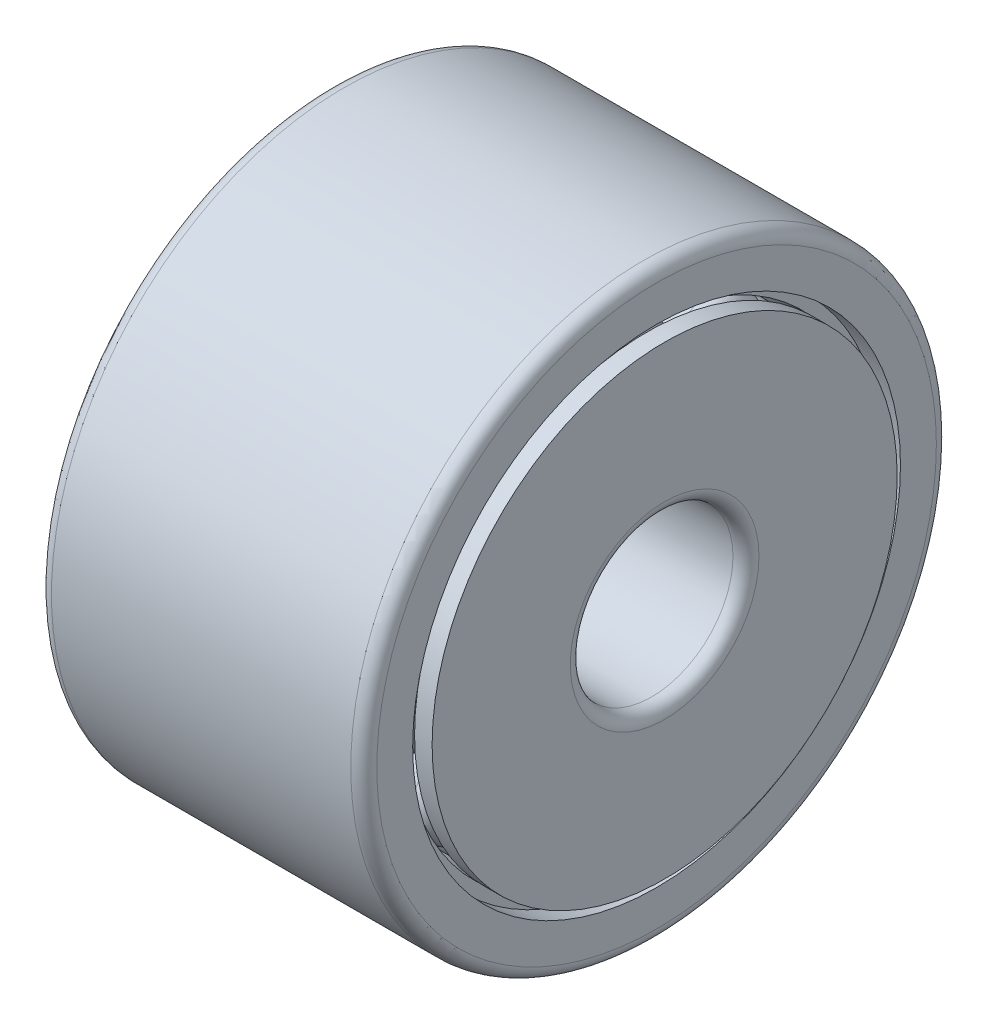
SolidWorks part; units mm, degrees
ref_plane "Plane1" through (0, 0, 0) normal (0, 0, 1) x (1, 0, 0)
ref_plane "Plane2" through (0, 0, 0) normal (0, 1, 0) x (1, 0, 0)
ref_plane "Plane3" through (0, 0, 0) normal (1, 0, 0) x (0, 0, -1)
sketch "Clipboard" plane through (0, 0, 0) normal (0, 0, 1) x (1, 0, 0)
  line L0 (-10, 0) -> (10, 0) construction
  line L1 (0, 0) -> (27.0344, -5.7463)
  line L2 (0, 0) -> (22.4793, 28.7722)
  line L3 (0, 0) -> (27.9428, -35.7651)
  line L4 (0, 0) -> (-22.3471, -0.7804)
  dimension "Race_OD" = 45.3866
  dimension "Race_ID" = 27.6384
sketch "OutRacSke" plane through (0, 0, 0) normal (0, 0, 1) x (1, 0, 0)
  line L0 (-14.0229, 22.6933) -> (-14.0229, 23.8026)
  line L1 (-14.0229, 23.8026) -> (-15.875, 23.8026)
  line L2 (-15.875, 23.8026) -> (-15.875, 27.305)
  line L3 (-14.605, 28.575) -> (14.605, 28.575)
  line L4 (15.875, 27.305) -> (15.875, 23.8026)
  line L5 (15.875, 23.8026) -> (14.0229, 23.8026)
  line L6 (14.0229, 23.8026) -> (14.0229, 22.6933)
  line L7 (14.0229, 22.6933) -> (-14.0229, 22.6933)
  line L8 (-7.9375, 0) -> (7.9375, 0) construction
  arc A0 (-15.875, 27.305) -> (-14.605, 28.575) centre (-14.605, 27.305) cw
  arc A1 (14.605, 28.575) -> (15.875, 27.305) centre (14.605, 27.305) cw
  dimension "D1" = 14.0229
  dimension "Race_OD" = 45.3866
  dimension "Cyl_Len" = 28.0458
revolve "OuterRace" add sketch "OutRacSke" angle 360 about L8
sketch "RolDetSke" plane through (0, 0, 0) normal (0, 0, 1) x (1, 0, 0)
  line L0 (-14.0229, 20.9188) -> (-14.0229, 18.2562)
  line L1 (-14.0229, 18.2562) -> (14.0229, 18.2562)
  line L2 (14.0229, 18.2562) -> (14.0229, 20.9188)
  line L3 (12.2479, 22.6938) -> (-12.2479, 22.6938)
  line L4 (-28.575, 18.2562) -> (28.575, 18.2562) construction
  arc A0 (14.0229, 20.9188) -> (12.2479, 22.6938) centre (12.2479, 20.9188) ccw
  arc A1 (-12.2479, 22.6938) -> (-14.0229, 20.9188) centre (-12.2479, 20.9188) ccw
  dimension "Cyl_Len" = 28.0458
  dimension "radius" = 1.775
  dimension "Roller_diameter" = 8.8751
revolve "RollerDetailed" add sketch "RolDetSke" angle 360 about L4
ref_axis "Axis1" through (-50, 0, 0) along (1, 0, 0)
pattern_circular "RollersDetailed" count 12 every 30 about axis through (-50, 0, 0) along (1, 0, 0) of "RollerDetailed", "OuterRace"
sketch "RolSimSke" plane through (0, 25.4, 0) normal (0, 0, 1) x (1, 0, 0)
  line L0 (-14.0229, -4.4807) -> (-14.0229, -9.8058)
  line L1 (-25.4, -25.4) -> (25.4, -25.4) construction
  line L2 (14.0229, -9.8058) -> (14.0229, -4.4807)
  line L3 (12.2479, -2.7057) -> (-12.2479, -2.7057)
  line L5 (12.2479, -11.5808) -> (-12.2479, -11.5808)
  arc A0 (14.0229, -4.4807) -> (12.2479, -2.7057) centre (12.2479, -4.4807) ccw
  arc A1 (-12.2479, -2.7057) -> (-14.0229, -4.4807) centre (-12.2479, -4.4807) ccw
  arc A2 (14.0229, -9.8058) -> (12.2479, -11.5808) centre (12.2479, -9.8058) cw
  arc A3 (-12.2479, -11.5808) -> (-14.0229, -9.8058) centre (-12.2479, -9.8058) cw
  dimension "radius" = 1.775
  dimension "Roller_diameter" = 8.8751
  dimension "Cyl_Len" = 28.0458
revolve "RollersSimplified" [suppressed] add sketch "RolSimSke" angle 360 about L1
sketch "InsRacSke" plane through (0, 0, 0) normal (0, 0, 1) x (1, 0, 0)
  line L0 (-14.949, 13.8192) -> (-14.949, 22.6933)
  line L1 (-14.949, 22.6933) -> (-16.6624, 22.6933)
  line L2 (-16.6624, 22.6933) -> (-16.6624, 9.2075)
  line L3 (-15.3924, 7.9375) -> (-0.84, 7.9375)
  line L4 (0.84, 7.9375) -> (15.3924, 7.9375)
  line L5 (16.6624, 9.2075) -> (16.6624, 22.6933)
  line L6 (16.6624, 22.6933) -> (14.949, 22.6933)
  line L7 (14.949, 22.6933) -> (14.949, 13.8192)
  line L8 (14.949, 13.8192) -> (-14.949, 13.8192)
  line L9 (-7.9375, 0) -> (7.9375, 0) construction
  arc A0 (-16.6624, 9.2075) -> (-15.3924, 7.9375) centre (-15.3924, 9.2075) ccw
  arc A1 (-0.84, 7.9375) -> (0.84, 7.9375) centre (0, 6.985) cw
  arc A2 (15.3924, 7.9375) -> (16.6624, 9.2075) centre (15.3924, 9.2075) ccw
  dimension "radius" = 1.27
  dimension "Bore" = 15.875
  dimension "halfWidth" = 16.6624
  dimension "Race_OD" = 45.3866
  dimension "Race_ID" = 27.6384
  dimension "SlotWidth" = 29.8979
revolve "InnerRace" add sketch "InsRacSke" angle 360 about L9
equation "\"halfWidth@OutRacSke\" =  \"Width@OutRacSke\" / 2"
equation "\"CLdia@Clipboard\" =  ( \"Race_OD@Clipboard\" + \"Race_ID@Clipboard\" )  / 2"
equation "\"CLRad@RolDetSke\" = ( \"Race_OD@Clipboard\" + \"Race_ID@Clipboard\" )  / 4"
equation "\"Roller_diameter@RolDetSke\" =  ( \"Race_OD@Clipboard\" -  \"Race_ID@Clipboard\" )  / 2 + .001"
equation "\"Roller_diameter@RolSimSke\" = ( \"Race_OD@Clipboard\" -  \"Race_ID@Clipboard\" )  / 2 + .001"
equation "\"radius@RolDetSke\" = \"Roller_diameter@RolDetSke\" / 5"
equation "\"radius@RolSimSke\" = \"Roller_diameter@RolSimSke\" / 5"
equation "\"Cyl_Len@OutRacSke\" = \"Cyl_Len@RolDetSke\""
equation "\"Cyl_Len@RolSimSke\" = \"Cyl_Len@RolDetSke\""
equation "\"halfCylLen@RolDetSke\" = \"Cyl_Len@RolDetSke\" / 2"
equation "\"offset@InsRacSke\" = \"radius@InsRacSke\" * 0.75"
equation "\"SlotWidth@InsRacSke\" =  ( \"Width@OutRacSke\" + \"Cyl_Len@RolDetSke\" )  / 2"
equation "\"halfSlotWidth@InsRacSke\" = \"SlotWidth@InsRacSke\" / 2"
equation "\"D1@OutRacSke\" = \"Cyl_Len@OutRacSke\" / 2"
equation "\"Max_count@Clipboard\" = int( 3.14159265 / atn(( \"Roller_diameter@RolDetSke\" / 2) / sqr( \"CLRad@RolDetSke\"  *  \"CLRad@RolDetSke\" - ( \"Roller_diameter@RolDetSke\" / 2) *  ( \"Roller_diameter@RolDetSke\" / 2))))"
equation "\"Max_count@Clipboard\" = ((sgn( \"Max_count@Clipboard\" - \"Count@Clipboard\" )-1)*( \"Max_count@Clipboard\" - \"Count@Clipboard\" ))/-2+ \"Count@Clipboard\""
equation "\"Count@RollersDetailed\" = int( \"Show_count@Clipboard\" ) "
equation "\"Count@RollersDetailed\" = ((sgn( \"Count@RollersDetailed\" - \"Max_count@Clipboard\" )-1)*( \"Count@RollersDetailed\" - \"Max_count@Clipboard\" ))/-2+ \"Max_count@Clipboard\""
equation "\"Count@RollersDetailed\" = ((sgn( \"Count@RollersDetailed\" - \"Min_count@Clipboard\" )+1)*( \"Count@RollersDetailed\" - \"Min_count@Clipboard\"))/2 +\"Min_count@Clipboard\""
equation "\"Angle@RollersDetailed\" = 360.0 / \"Max_count@Clipboard\""
equation "\"Bore@RolSimSke\" = \"Race_ID@Clipboard\""
equation "\"Race_ID@InsRacSke\" = \"Race_ID@Clipboard\""
equation "\"Race_OD@InsRacSke\" = \"Race_OD@Clipboard\""
equation "\"halfWidth@InsRacSke\" = \"Width_IR@InsRacSke\" / 2"
equation "\"halfLength@RolSimSke\" = \"Cyl_Len@RolSimSke\" / 2"
equation "\"Race_OD@OutRacSke\" = \"Race_OD@Clipboard\""
